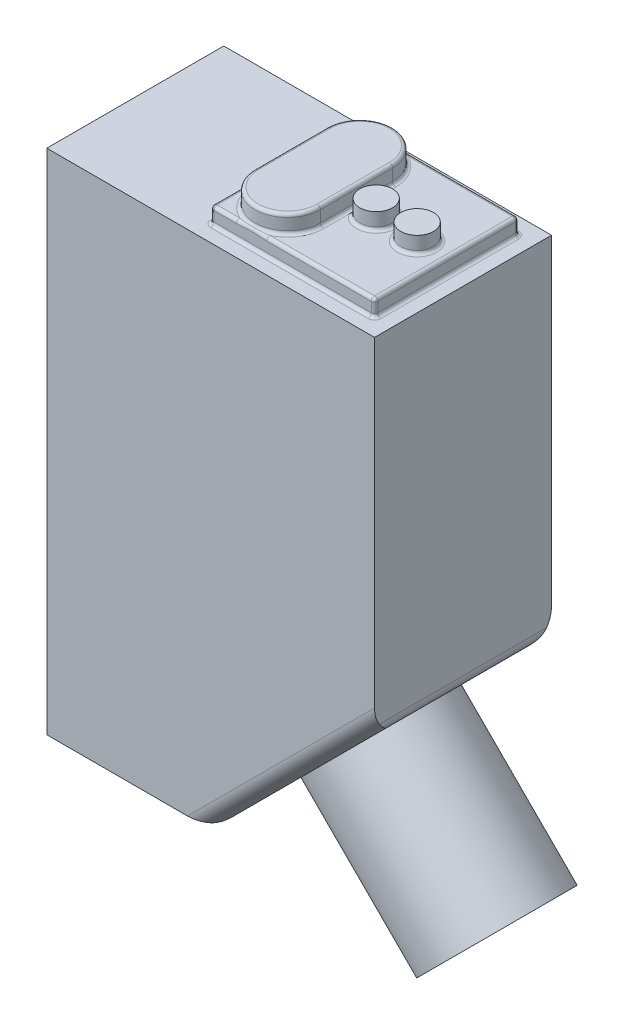
SolidWorks part; units mm, degrees
ref_plane "前视基准面" through (0, 0, 0) normal (0, 0, 1) x (1, 0, 0)
ref_plane "上视基准面" through (0, 0, 0) normal (0, 1, 0) x (1, 0, 0)
ref_plane "右视基准面" through (0, 0, 0) normal (1, 0, 0) x (0, 0, -1)
sketch "草图1" plane through (0, 0, 0) normal (0, 1, 0) x (1, 0, 0)
  line L1 (-10, 5.4) -> (10, 5.4)
  line L2 (-10, 5.4) -> (-10, -5.4)
  line L3 (-10, -5.4) -> (10, -5.4)
  line L4 (10, 5.4) -> (10, -5.4)
  line L5 (-10, 5.4) -> (10, -5.4) construction
  line L6 (-10, -5.4) -> (10, 5.4) construction
  point P0 (0, 0)
  dimension "D1" = 20
  dimension "D2" = 10.8
extrude "凸台-拉伸1" add sketch "草图1" along normal blind 31
sketch "草图2" plane through (0, 0, 5.4) normal (0, 0, 1) x (1, 0, 0)
  line L0 (0, 0) -> (10, 10)
  line L1 (10, 31) -> (10, 0) construction
  line L3 (10, 10) -> (10, 0)
  line L4 (10, 0) -> (0, 0)
  dimension "D1" = 14.1421
extrude "切除-拉伸1" cut sketch "草图2" against normal up to next
sketch "草图3" plane through (0, 0, 0) normal (0.7071, -0.7071, 0) x (0, 0, -1)
  line L0 (-5.4, 14.1421) -> (5.4, 0) construction
  line L1 (5.4, 0) -> (-5.4, 0) construction
  line L2 (5.4, 0) -> (5.4, -7.0711) construction
  line L3 (5.4, 14.1421) -> (-5.4, 0) construction
  circle A0 centre (0, 7.0711) radius 4
extrude "凸台-拉伸2" add sketch "草图3" along normal blind 10
sketch "草图4" plane through (-10, 0, 0) normal (-1, 0, 0) x (0, 0, 1)
  line L0 (0, 31) -> (0, 0) construction
  line L1 (-5.4, 31) -> (5.4, 31) construction
  line L2 (0, 21.398) -> (0, 9.602) construction
  line L3 (-4, 24.5) -> (4, 24.5)
  line L4 (-4, 24.5) -> (-4, 6.5)
  line L5 (-4, 6.5) -> (4, 6.5)
  line L6 (4, 24.5) -> (4, 6.5)
  line L7 (-4, 24.5) -> (4, 6.5) construction
  line L8 (-4, 6.5) -> (4, 24.5) construction
  line L9 (2.8369, 21.398) -> (2.8369, 9.602)
  line L10 (-2.8369, 21.398) -> (-2.8369, 9.602)
  arc A0 (2.8369, 21.398) -> (-2.8369, 21.398) centre (0, 21.398) ccw
  arc A1 (-2.8369, 9.602) -> (2.8369, 9.602) centre (0, 9.602) ccw
  point P5 (0, 15.5)
  point P12 (0, 15.5)
  dimension "D1" = 18
  dimension "D2" = 8
extrude "切除-拉伸2" cut sketch "草图4" against normal blind 5
fillet "圆角2" radius 1 4 edges at (5, 5, -5.4) (0, 0, 0) (5, 5, 5.4) (10, 10, 0)
sketch "草图5" plane through (0, 31, 0) normal (0, 1, 0) x (1, 0, 0)
  line L1 (-1, 4.4) -> (9, 4.4)
  line L2 (-1, 4.4) -> (-1, -4.4)
  line L3 (-1, -4.4) -> (9, -4.4)
  line L4 (9, 4.4) -> (9, -4.4)
  line L9 (-10, -5.4) -> (10, -5.4) construction
  line L10 (10, 5.4) -> (-10, 5.4) construction
  line L11 (10, -5.4) -> (10, 5.4) construction
  dimension "D1" = 10
  dimension "D2" = 1
  dimension "D3" = 1
  dimension "D4" = 1
extrude "凸台-拉伸3" add sketch "草图5" along normal blind 1
sketch "草图6" plane through (0, 32, 0) normal (0, 1, 0) x (1, 0, 0)
  line L0 (1.5, 2.2) -> (1.5, -2.2) construction
  line L2 (3.5, 2.2) -> (3.5, -2.2)
  line L3 (1.5, 0) -> (1.5, 4.4) construction
  line L5 (-0.5, 2.2) -> (-0.5, -2.2)
  line L6 (-1, -4.4) -> (9, -4.4) construction
  arc A0 (3.5, 2.2) -> (-0.5, 2.2) centre (1.5, 2.2) ccw
  arc A1 (-0.5, -2.2) -> (3.5, -2.2) centre (1.5, -2.2) ccw
  point P2 (1.5, 0)
  dimension "D3" = 2
  dimension "D1" = 2.2
  dimension "D2" = 2.2
extrude "凸台-拉伸4" add sketch "草图6" along normal blind 1.1
sketch "草图7" plane through (0, 32, 0) normal (0, 1, 0) x (1, 0, 0)
  line L0 (-1, 0) -> (9, 0) construction
  line L1 (-1, 4.4) -> (-1, -4.4) construction
  line L3 (3.5, -2.2) -> (3.5, 2.2) construction
  circle A0 centre (4.7, 0) radius 1
  circle A1 centre (7.2, 0) radius 1
  dimension "D1" = 2
  dimension "D2" = 1.2
  dimension "D3" = 2
extrude "凸台-拉伸5" add sketch "草图7" along normal blind 1
fillet "圆角4" radius 0.2 8 edges at (-0.5, 32, 0) (1.5, 32, -4.2) (3.5, 32, 0) (1.5, 32, 4.2) (3.5, 33.1, 0) (1.5, 33.1, -4.2) (-0.5, 33.1, 0) (1.5, 33.1, 4.2)
fillet "圆角5" radius 0.2 16 edges at (7.2, 32, 1) (4.7, 32, 1) (-1, 31, 0) (-1, 32, 0) (0.25, 32, 4.4) (9, 32, 0) (0.25, 32, -4.4) (5.25, 32, -4.4) (-1, 31.5, -4.4) (9, 31.5, -4.4) (9, 31.5, 4.4) (-1, 31.5, 4.4) (5.25, 32, 4.4) (9, 31, 0) (4, 31, -4.4) (4, 31, 4.4)
sketch "草图8" plane through (0, 0, 5.4) normal (0, 0, 1) x (1, 0, 0)
  line L0 (-6.5, 31) -> (-6.5, 0) construction
  line L1 (-10, 31) -> (10, 31) construction
  line L2 (-10, 0) -> (-1.4142, 0) construction
  line L3 (-10, 31) -> (-10, 0) construction
  circle A2 centre (-6.5, 27.5) radius 3
  circle A3 centre (-6.5, 3.5) radius 3
  dimension "D3" = 6
  dimension "D2" = 6
  dimension "D1" = 3.5
  dimension "D4" = 24
  dimension "D5" = 3.5
sketch "草图9" plane through (0, 0, -5.4) normal (0, 0, -1) x (-1, 0, 0)
  circle A0 centre (6.5, 3.5) radius 3 construction
  circle A1 centre (6.5, 27.5) radius 3 construction
  circle A2 centre (6.5, 3.5) radius 3
  circle A3 centre (6.5, 27.5) radius 3
hole_wizard "M3 螺纹孔1" positions "草图10" profile "草图11" tap size "M3" standard "GB"
sketch "草图10" plane through (0, 0, -5.4) normal (0, 0, -1) x (-1, 0, 0)
  point P0 (6.5, 27.5)
  point P3 (6.5, 3.5)
sketch "草图11" plane through (-6.5, 27.5, -5.4) normal (1, 0, 0) x (0, 1, 0)
  line L0 (0, 0) -> (0, 5.7511)
  line L1 (0, 5.7511) -> (1.25, 5)
  line L2 (1.25, 5) -> (1.25, 0)
  line L5 (1.25, 0) -> (0, 0)
  line L10 (0, 5.7511) -> (-1.25, 5) construction
  line L11 (0, -6.35) -> (0, 107.95) construction
  dimension "螺纹孔钻头直径" = 2.5
  dimension "螺纹孔钻头深度" = 5
  dimension "导头角度" = 118
cosmetic thread "孔螺蚊线1"
cosmetic thread "孔螺蚊线2"
